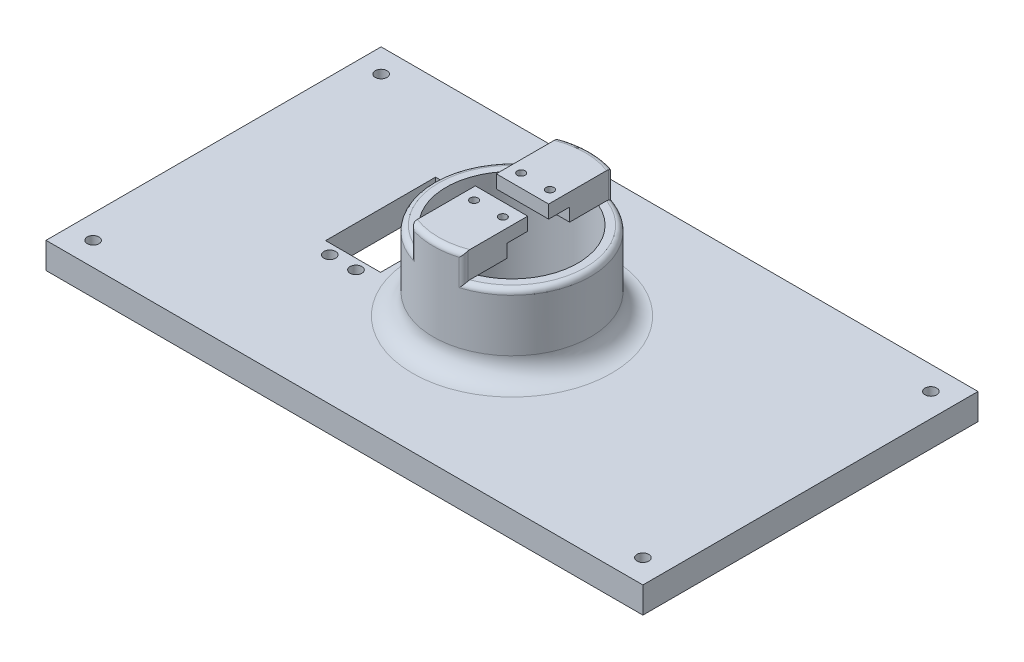
SolidWorks part; units mm, degrees
note: '?' marks a value the reader was unsure of.
ref_plane "Front Plane" through (0, 0, 0) normal (0, 0, 1) x (1, 0, 0)
ref_plane "Top Plane" through (0, 0, 0) normal (0, 1, 0) x (1, 0, 0)
ref_plane "Right Plane" through (0, 0, 0) normal (1, 0, 0) x (0, 0, -1)
sketch "Sketch1" plane through (0, 0, 0) normal (0, 1, 0) x (1, 0, 0)
  line L0 (0, 100.3898) -> (0, -103.8011) construction
  line L1 (-104.3339, 0) -> (101.319, 0) construction
  line L3 (-114, -64) -> (114, -64)
  line L4 (-114, -64) -> (-114, 64)
  line L5 (-114, 64) -> (114, 64)
  line L6 (114, -64) -> (114, 64)
  line L7 (-114, -64) -> (114, 64) construction
  line L8 (-114, 64) -> (114, -64) construction
  point P5 (0, 0)
  dimension "D1" = 228
  dimension "D2" = 128
extrude "Boss-Extrude1" add sketch "Sketch1" along normal blind 10
sketch "Sketch2" plane through (0, 10, 0) normal (0, 1, 0) x (1, 0, 0)
  circle A0 centre (0, 0) radius 30
  dimension "D1" = 60
extrude "Boss-Extrude2" add sketch "Sketch2" along normal blind 30
sketch "Sketch3" plane through (0, 40, 0) normal (0, 1, 0) x (1, 0, 0)
  circle A0 centre (0, 0) radius 25.15
  dimension "D1" = 50.3
extrude "Cut-Extrude1" cut sketch "Sketch3" against normal through all
sketch "Sketch4" plane through (0, 40, 0) normal (0, 1, 0) x (1, 0, 0)
  line L0 (-30, 0) -> (30, 0) construction
  line L1 (-28.6182, 9) -> (28.6182, 9) construction
  line L2 (0, 30) -> (0, -30) construction
  line L3 (-10, 28.2843) -> (-10, 4)
  line L4 (-10, 4) -> (10, 4)
  line L5 (10, 28.2843) -> (10, 4)
  line L6 (-10, -4) -> (10, -4)
  line L7 (10, -28.2843) -> (10, -4)
  line L8 (-10, -28.2843) -> (-10, -4)
  circle A0 centre (0, 0) radius 30 construction
  circle A1 centre (0, 0) radius 30 construction
  arc A3 (10, 28.2843) -> (-10, 28.2843) centre (0, 0) ccw
  arc A4 (10, -28.2843) -> (-10, -28.2843) centre (0, 0) cw
  circle A5 centre (-5.5, 9) radius 1.5
  circle A6 centre (5.5, 9) radius 1.5
  circle A7 centre (5.5, -9) radius 1.5
  circle A8 centre (-5.5, -9) radius 1.5
  point P15 (0, 4)
  dimension "D5" = 3
  dimension "D1" = 9
  dimension "D2" = 20
  dimension "D3" = 8
  dimension "D4" = 11
extrude "Boss-Extrude3" add sketch "Sketch4" along normal blind 10
sketch "Sketch5" plane through (-10, 0, 0) normal (-1, 0, 0) x (0, 0, 1)
  line L0 (0, 40) -> (0, 57.6327) construction
  line L1 (28.2843, 40) -> (-28.2843, 40) construction
  line L2 (-12, 40) -> (-12, 45)
  line L3 (-23.0764, 40) -> (-4, 40) construction
  line L4 (-12, 45) -> (12, 45)
  line L5 (-12, 40) -> (12, 40)
  line L6 (12, 40) -> (12, 45)
  point P11 (0, 45)
  dimension "D1" = 24
  dimension "D2" = 5
extrude "Cut-Extrude2" cut sketch "Sketch5" against normal up to next
fillet "Fillet1" radius 8 1 edges at (0, 10, 30)
fillet "Fillet2" radius 2 8 edges at (-10, 45, 28.2843) (0, 50, 30) (10, 45, 28.2843) (30, 40, 0) (10, 45, -28.2843) (0, 50, -30) (-10, 45, -28.2843) (-30, 40, 0)
sketch "Sketch6" plane through (0, 10, 0) normal (0, 1, 0) x (1, 0, 0)
  line L0 (-114, 0) -> (114, 0) construction
  line L1 (-114, 64) -> (-114, -64) construction
  line L2 (114, -64) -> (114, 64) construction
  line L3 (0, 64) -> (0, -64) construction
  line L4 (114, 64) -> (-114, 64) construction
  line L5 (-114, -64) -> (114, -64) construction
  circle A0 centre (-105, 55) radius 2.25
  circle A1 centre (105, 55) radius 2.25
  circle A2 centre (105, -55) radius 2.25
  circle A3 centre (-105, -55) radius 2.25
  dimension "D3" = 4.5
  dimension "D1" = 210
  dimension "D2" = 110
extrude "Cut-Extrude3" cut sketch "Sketch6" against normal through all
sketch "Sketch7" plane through (0, 10, 0) normal (0, 1, 0) x (1, 0, 0)
  line L0 (0, 0) -> (-69.9739, 0) construction
  line L1 (-64.5487, 10.3) -> (-41.63, 10.3) construction
  line L2 (-50, 44.6194) -> (-50, -34.5441) construction
  line L4 (-60.5, -10.7) -> (-39.5, -10.7)
  line L5 (-60.5, -10.7) -> (-60.5, 31.3)
  line L6 (-60.5, 31.3) -> (-39.5, 31.3)
  line L7 (-39.5, -10.7) -> (-39.5, 31.3)
  line L8 (-60.5, -10.7) -> (-39.5, 31.3) construction
  line L9 (-60.5, 31.3) -> (-39.5, -10.7) construction
  circle A0 centre (-55, 35.2) radius 2.25
  circle A1 centre (-45, 35.2) radius 2.25
  circle A2 centre (-45, -14.6) radius 2.25
  circle A3 centre (-55, -14.6) radius 2.25
  point P7 (-50, 10.3)
  point P8 (-50, 10.3)
  dimension "D5" = 4.5
  dimension "D1" = 10.3
  dimension "D2" = 50
  dimension "D3" = 21
  dimension "D4" = 42
  dimension "D6" = 10
  dimension "D7" = 49.8
extrude "Cut-Extrude4" cut sketch "Sketch7" against normal through all
ref_axis "Axis1" through (0, 0, 0) along (0, 1, 0)?
